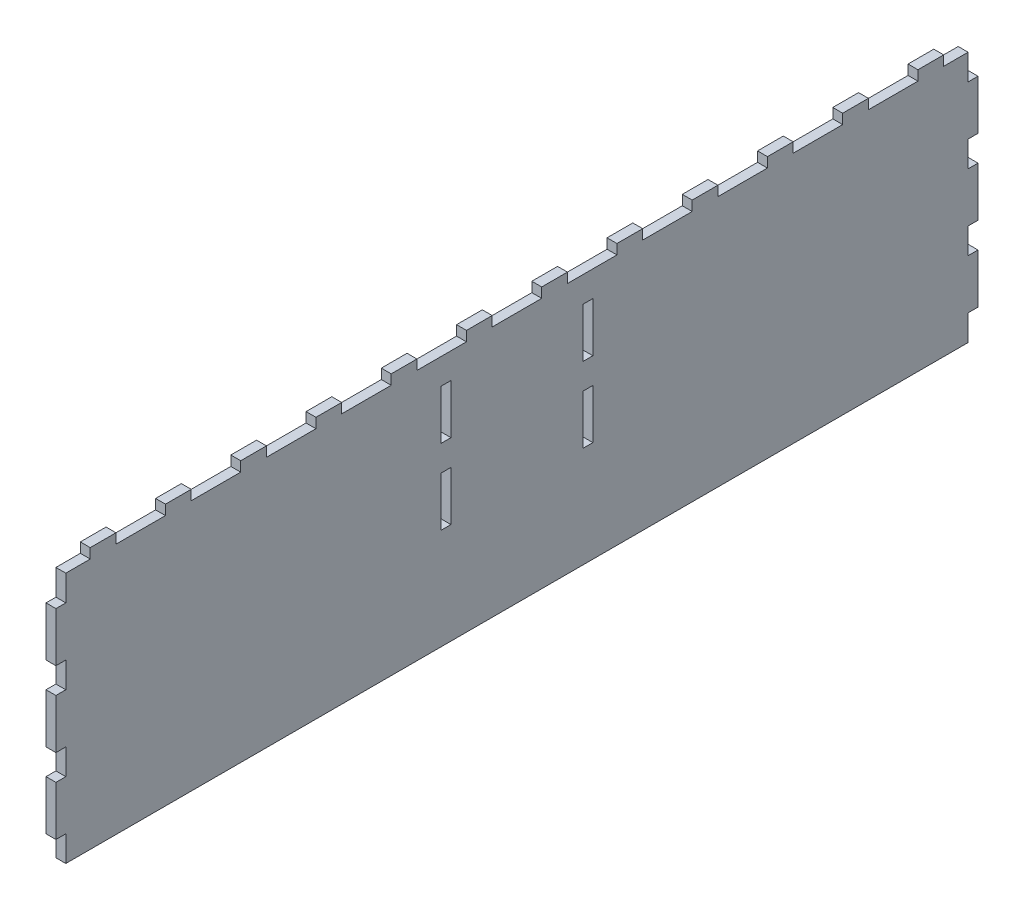
SolidWorks part; units mm, degrees
material "ENPH 253 Hardboard"
ref_plane "Front Plane" through (0, 0, 0) normal (0, 0, 1) x (1, 0, 0)
ref_plane "Top Plane" through (0, 0, 0) normal (0, 1, 0) x (1, 0, 0)
ref_plane "Right Plane" through (0, 0, 0) normal (1, 0, 0) x (0, 0, -1)
sketch "Sketch1" plane through (0, 0, 0) normal (1, 0, 0) x (0, 0, -1)
  line L1 (-139.7, 38.1) -> (139.7, 38.1)
  line L2 (-139.7, 38.1) -> (-139.7, -38.1)
  line L3 (-139.7, -38.1) -> (139.7, -38.1)
  line L4 (139.7, 38.1) -> (139.7, -38.1)
  line L5 (-139.7, 38.1) -> (139.7, -38.1) construction
  line L6 (-139.7, -38.1) -> (139.7, 38.1) construction
  point P0 (0, 0)
  dimension "D1" = 279.4
  dimension "D2" = 76.2
extrude "Boss-Extrude1" add sketch "Sketch1" against normal blind 3 contours L2 L3 L4 L1
sketch "Sketch3" plane through (-3, 0, 0) normal (-1, 0, 0) x (0, 0, 1)
  line L9 (-139.7, 38.1) -> (-136.7, 38.1)
  line L10 (-139.7, 38.1) -> (-139.7, 30.3)
  line L11 (-139.7, 30.3) -> (-136.7, 30.3)
  line L12 (-136.7, 38.1) -> (-136.7, 30.3)
  dimension "D9" = 7.8
  dimension "D10" = 3
extrude "Cut-Extrude1" cut sketch "Sketch3" against normal through all
pattern_linear "LPattern1" count 4 spacing 22.8 along (0, -1, 0) of "Cut-Extrude1"
mirror "Mirror1" about plane through (0, 0, 0) normal (0, 0, 1) of "LPattern1"
sketch "Sketch5" plane through (-3, 0, 0) normal (-1, 0, 0) x (0, 0, 1)
  line L1 (-23, 30.3) -> (-20, 30.3)
  line L2 (-23, 30.3) -> (-23, 15.3)
  line L3 (-23, 15.3) -> (-20, 15.3)
  line L4 (-20, 30.3) -> (-20, 15.3)
  line L5 (136.7, 38.1) -> (-136.7, 38.1) construction
  line L6 (0, -1.65) -> (0, 1.65) construction
  dimension "D1" = 20
  dimension "D2" = 3
  dimension "D3" = 7.8
  dimension "D4" = 15
extrude "Cut-Extrude3" cut sketch "Sketch5" against normal blind 10
sketch "Sketch9" plane through (0, 38.1, 0) normal (0, 1, 0) x (1, 0, 0)
  line L0 (0, -136.7) -> (0, 136.7) construction
  line L1 (0, 129.3) -> (-3, 129.3)
  line L2 (0, 129.3) -> (0, 121.5)
  line L3 (0, 121.5) -> (-3, 121.5)
  line L4 (-3, 129.3) -> (-3, 121.5)
  line L5 (-3, -136.7) -> (-3, 136.7) construction
  line L6 (0, 136.7) -> (-3, 136.7) construction
  point P10 (-1.5, 129.3)
  dimension "D1" = 7.4
  dimension "D2" = 7.8
extrude "Boss-Extrude2" add sketch "Sketch9" along normal blind 3
pattern_linear "LPattern4" count 12 spacing 22.8 along (0, 0, 1) of "Boss-Extrude2"
pattern_linear "LPattern5" count 2 spacing 22.8 along (0, -1, 0) of "Cut-Extrude3"
mirror "Mirror2" about plane through (0, 0, 0) normal (0, 0, 1) of "LPattern5"
